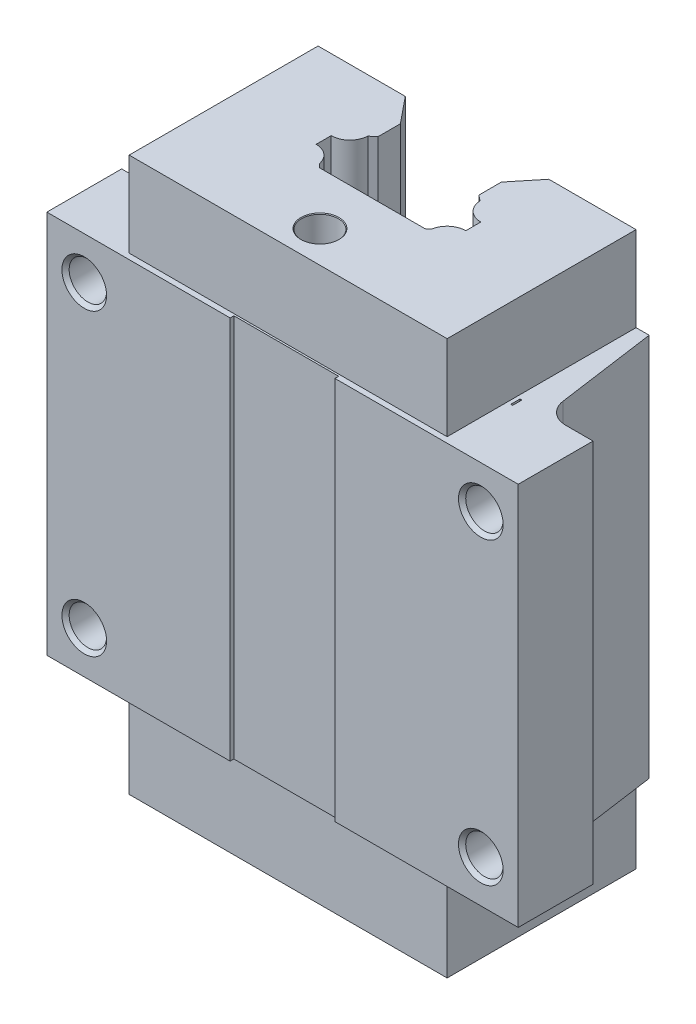
SolidWorks part; units mm, degrees
material "5086-H32, Stange (SS)"
ref_plane "Ebene vorne" through (0, 0, 0) normal (0, 0, 1) x (1, 0, 0)
ref_plane "Ebene oben" through (0, 0, 0) normal (0, 1, 0) x (1, 0, 0)
ref_plane "Ebene rechts" through (0, 0, 0) normal (1, 0, 0) x (0, 0, -1)
ref_plane "Ebene1" through (0, 0, 4) normal (0, 0, -1) x (-1, 0, 0)
sketch "Skizze1" plane through (0, 0, 4) normal (0, 0, -1) x (-1, 0, 0)
  line L0 (-22, -25.65) -> (22, -25.65)
  line L1 (22, -25.65) -> (22, 25.65)
  line L2 (22, 25.65) -> (-22, 25.65)
  line L3 (-22, 25.65) -> (-22, -25.65)
  line L4 (0, 0) -> (0, 28.4988) construction
  line L5 (0, 0) -> (24.5295, 0) construction
  dimension "D1" = 44
  dimension "D2" = 51.3
extrude "Aufsatz-Linear austragen1" add sketch "Skizze1" against normal blind 26
sketch "Skizze2" plane through (0, -25.65, 0) normal (0, -1, 0) x (1, 0, 0)
  line L0 (-21.75, 4) -> (-21.75, 21.25)
  line L1 (-21.75, 21.25) -> (-22, 21.25)
  line L2 (-22, 21.25) -> (-22, 4)
  line L3 (-22, 4) -> (-21.75, 4)
  dimension "D1" = 0.25
  dimension "D2" = 17.25
extrude "Schnitt-Linear austragen1" cut sketch "Skizze2" against normal through all
sketch "Skizze3" plane through (0, -25.65, 0) normal (0, -1, 0) x (1, 0, 0)
  line L0 (7, 30) -> (-7, 30)
  line L1 (-7, 30) -> (-7, 29.5)
  line L2 (-7, 29.5) -> (7, 29.5)
  line L3 (7, 29.5) -> (7, 30)
extrude "Schnitt-Linear austragen2" cut sketch "Skizze3" against normal through all
sketch "Skizze4" plane through (0, -25.65, 0) normal (0, -1, 0) x (1, 0, 0)
  line L0 (22, 21.25) -> (21.75, 21.25)
  line L1 (21.75, 21.25) -> (21.75, 4)
  line L2 (21.75, 4) -> (22, 4)
  line L3 (22, 4) -> (22, 21.25)
extrude "Schnitt-Linear austragen3" cut sketch "Skizze4" against normal blind 51.3
sketch "Skizze5" plane through (0, 25.65, 0) normal (0, 1, 0) x (-1, 0, 0)
  line L0 (21.25, 4) -> (-21.25, 4)
  line L1 (-21.25, 4) -> (-21.25, 29.25)
  line L2 (-21.25, 29.25) -> (21.25, 29.25)
  line L3 (21.25, 29.25) -> (21.25, 4)
extrude "Aufsatz-Linear austragen2" add sketch "Skizze5" along normal blind 11.35
sketch "Skizze6" plane through (0, -25.65, 0) normal (0, -1, 0) x (1, 0, 0)
  line L0 (21.25, 4) -> (-21.25, 4)
  line L1 (-21.25, 4) -> (-21.25, 29.25)
  line L2 (-21.25, 29.25) -> (21.25, 29.25)
  line L3 (21.25, 29.25) -> (21.25, 4)
extrude "Aufsatz-Linear austragen3" add sketch "Skizze6" along normal blind 11.35
sketch "Skizze15" plane through (0, 0, 30) normal (0, 0, 1) x (1, 0, 0)
  line L0 (0, 0) -> (0, 38.9131) construction
  line L1 (-7, -25.65) -> (-22, -25.65) construction
  line L2 (-22, 25.65) -> (-31.5, 25.65)
  line L3 (-22, 25.65) -> (-22, -25.65)
  line L4 (-22, -25.65) -> (-31.5, -25.65)
  line L5 (-31.5, 25.65) -> (-31.5, -25.65)
  line L6 (22, 25.65) -> (22, -25.65)
  line L7 (22, -25.65) -> (31.5, -25.65)
  line L8 (31.5, 25.65) -> (31.5, -25.65)
  line L9 (22, 25.65) -> (31.5, 25.65)
  dimension "D1" = 63
extrude "Aufsatz-Linear austragen5" add sketch "Skizze15" against normal blind 10
sketch "Skizze7" plane through (0, -37, 0) normal (0, -1, 0) x (1, 0, 0)
  line L0 (-9.5938, 4) -> (9.5938, 4)
  line L1 (9.5938, 4) -> (6.75, 7.5)
  line L2 (6.75, 7.5) -> (6.75, 10.5)
  line L3 (6.75, 10.5) -> (7.5, 11.1094)
  line L4 (10, 13.5) -> (10, 15.5)
  line L5 (7.5, 18) -> (-7.5, 18)
  line L6 (-10, 15.5) -> (-10, 13.5)
  line L7 (-7.5, 11.1094) -> (-6.75, 10.5)
  line L8 (-6.75, 10.5) -> (-6.75, 7.5)
  line L9 (-6.75, 7.5) -> (-9.5938, 4)
  arc A0 (7.5, 11.1094) -> (10, 13.5) centre (10, 10.9975) cw
  arc A1 (10, 15.5) -> (7.5, 18) centre (10, 18) cw
  arc A2 (-7.5, 18) -> (-10, 15.5) centre (-10, 18) cw
  arc A3 (-10, 13.5) -> (-7.5, 11.1094) centre (-10, 10.9975) cw
extrude "Schnitt-Linear austragen4" cut sketch "Skizze7" against normal through all
hole_wizard "Bohrung1" positions "Skizze9" profile "Skizze8" legacy
sketch "Skizze9" plane through (0, -37, 0) normal (0, -1, 0) x (-1, 0, 0)
  point P0 (0, -25)
sketch "Skizze8" plane through (0, -37, 25) normal (1, 0, 0) x (0, 0, -1)
  line L0 (0, 0) -> (0, 16.4772)
  line L1 (0, 16.4772) -> (2.4585, 15)
  line L2 (2.4585, 15) -> (2.4585, 0)
  line L4 (2.4585, 0) -> (0, 0)
  line L6 (0, 16.4772) -> (-2.4585, 15) construction
  line L7 (0, -4.2442) -> (0, 117.3081) construction
  dimension "Durchmesser" = 4.917
  dimension "Tiefe" = 15
  dimension "Spitzenwinkel" = 118
hole_wizard "Bohrung2" positions "Skizze11" profile "Skizze10" legacy
sketch "Skizze11" plane through (0, 37, 0) normal (0, 1, 0) x (1, 0, 0)
  point P0 (0, -25)
sketch "Skizze10" plane through (0, 37, 25) normal (1, 0, 0) x (0, 0, 1)
  line L0 (0, 0) -> (0, 16.4772)
  line L1 (0, 16.4772) -> (2.4585, 15)
  line L2 (2.4585, 15) -> (2.4585, 0)
  line L4 (2.4585, 0) -> (0, 0)
  line L6 (0, 16.4772) -> (-2.4585, 15) construction
  line L7 (0, -4.2442) -> (0, 117.3081) construction
  dimension "Durchmesser" = 4.917
  dimension "Tiefe" = 15
  dimension "Spitzenwinkel" = 118
hole_wizard "M6 Gewindebohrung1" positions "Skizze13" profile "Skizze12" tap size "M6" standard "DIN"
sketch "Skizze13" plane through (0, 0, 30) normal (0, 0, 1) x (1, 0, 0)
  line L0 (0, 0) -> (0, 31.6755) construction
  line L3 (0, 0) -> (24.4826, 0) construction
  point P0 (26.5, -20)
  point P1 (26.5, 20)
  point P2 (-26.5, 20)
  point P3 (-26.5, -20)
  dimension "D1" = 53
  dimension "D2" = 40
sketch "Skizze12" plane through (26.5, -20, 30) normal (1, 0, 0) x (0, -1, 0)
  line L0 (0, 0) -> (0, 18.5022)
  line L1 (0, 18.5022) -> (2.5, 17)
  line L2 (2.5, 17) -> (2.5, 0)
  line L5 (2.5, 0) -> (0, 0)
  line L10 (0, 18.5022) -> (-2.5, 17) construction
  line L11 (0, -6.35) -> (0, 107.95) construction
  dimension "Bohrerdurchmesser" = 5
  dimension "Bohrungstiefe" = 17
  dimension "Spitzenwinkel" = 118
chamfer "Fase1" distance 0.483 angle 45 4 edges at (29, 20, 30) (-24, 20, 30) (29, -20, 30) (-24, -20, 30)
chamfer "Fase2" distance 0.449 angle 42.13 1 edges at (-7.5, 0, 18) first distance on face at (0, 0, 18)
chamfer "Fase3" distance 0.0915 angle 45 2 edges at (0, -37, 22.5415) (0, 37, 27.4585)
chamfer "Fase4" distance 0.449 angle 42.13 1 edges at (7.5, 0, 18) first distance on face at (0.2245, 0, 18)
sketch "Skizze16" plane through (0, -25.65, 0) normal (0, -1, 0) x (1, 0, 0)
  line L0 (0, 0) -> (0, 34.0951) construction
  line L1 (-21.75, 4) -> (-21.75, 20)
  line L2 (-21.75, 4) -> (-21.75, 21.25) construction
  line L3 (-21.75, 20) -> (-25.25, 20)
  line L4 (-25.25, 20) -> (-23, 4)
  line L5 (-23, 4) -> (-21.75, 4)
  line L6 (-31.5, 20) -> (-22, 20) construction
  line L7 (21.75, 20) -> (25.25, 20)
  line L8 (21.75, 4) -> (21.75, 20)
  line L9 (23, 4) -> (21.75, 4)
  line L10 (25.25, 20) -> (23, 4)
  dimension "D1" = 46
  dimension "D2" = 50.5
extrude "Aufsatz-Linear austragen6" add sketch "Skizze16" against normal up to surface (51.3 mm away) up to face at (0, 25.65, 20.925)
fillet "Verrundung1" radius 3 6 edges at (25.25, 23.9075, 20) (25.25, 0, 20) (25.25, -23.9075, 20) (-25.25, 23.9075, 20) (-25.25, -23.9075, 20) (-25.25, 0, 20)
